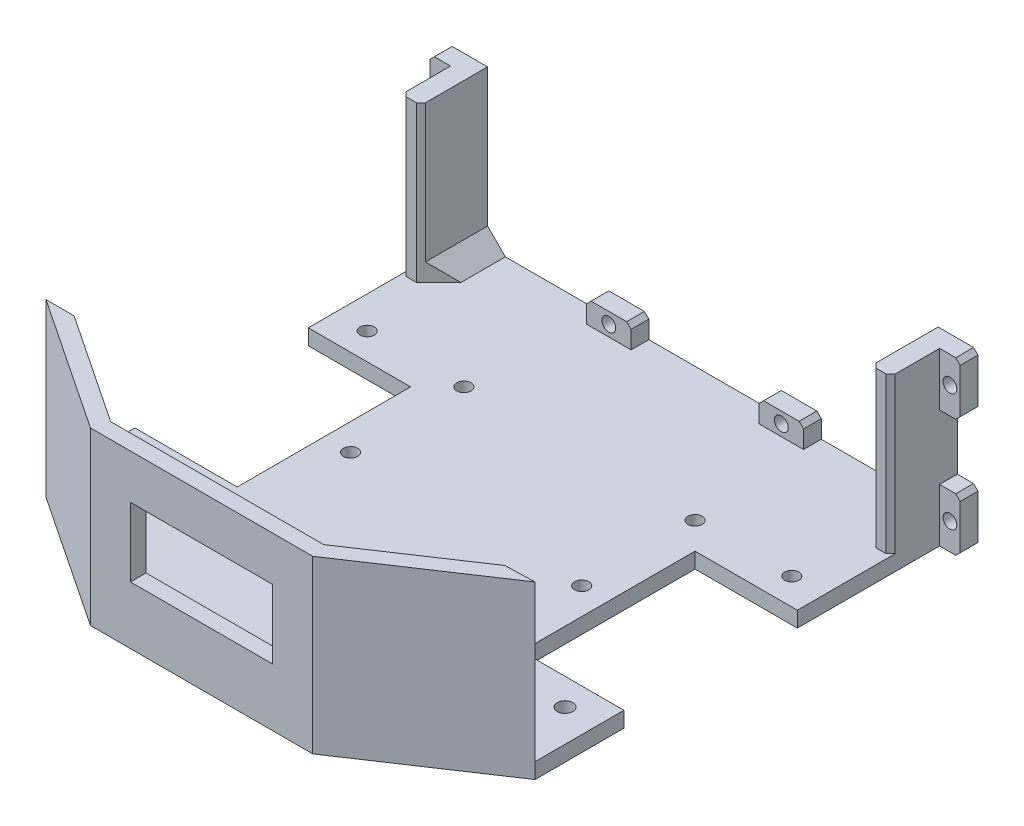
SolidWorks part; units mm, degrees
ref_plane "Front Plane" through (0, 0, 0) normal (0, 0, 1) x (1, 0, 0)
ref_plane "Top Plane" through (0, 0, 0) normal (0, 1, 0) x (1, 0, 0)
ref_plane "Right Plane" through (0, 0, 0) normal (1, 0, 0) x (0, 0, -1)
sketch "Sketch1" plane through (0, 0, 0) normal (0, 1, 0) x (1, 0, 0)
  line L0 (0, 40) -> (23, 40)
  line L1 (30, 0) -> (80, 0)
  line L2 (0, 20) -> (0, 40)
  line L3 (0, 100) -> (110, 100)
  line L4 (110, 20) -> (110, 40)
  line L5 (23, 40) -> (23, 79)
  line L6 (23, 79) -> (0, 79)
  line L7 (110, 79) -> (87, 79)
  line L8 (87, 79) -> (87, 40)
  line L9 (87, 40) -> (110, 40)
  line L10 (0, 79) -> (0, 100)
  line L11 (110, 79) -> (110, 100)
  line L12 (0, 20) -> (30, 0)
  line L13 (110, 20) -> (80, 0)
  point P0 (55, 0)
  dimension "D1" = 100
  dimension "D2" = 110
  dimension "23" = 23
  dimension "D4" = 40
  dimension "20" = 23
  dimension "D5" = 39
  dimension "40" = 40
extrude "Boss-Extrude1" add sketch "Sketch1" along normal blind 3.5 contours L1 L13 L4 L9 L8 L7 L11 L3 L10 L6 L5 L0 L2 L12
sketch "Sketch2" plane through (0, 3.5, 0) normal (0, 1, 0) x (1, 0, 0)
  line L0 (0, 79) -> (23, 79)
  line L1 (23, 79) -> (23, 40)
  line L2 (23, 40) -> (0, 40)
  line L3 (0, 40) -> (0, 37.5)
  line L4 (0, 40) -> (0, 20) construction
  line L5 (0, 37.5) -> (25.5, 37.5)
  line L6 (25.5, 37.5) -> (25.5, 81.5)
  line L7 (25.5, 81.5) -> (0, 81.5)
  line L8 (0, 100) -> (0, 79) construction
  line L9 (0, 81.5) -> (0, 79)
  line L10 (110, 81.5) -> (84.5, 81.5)
  line L11 (110, 79) -> (110, 100) construction
  line L12 (84.5, 81.5) -> (84.5, 37.5)
  line L13 (84.5, 37.5) -> (110, 37.5)
  line L14 (110, 20) -> (110, 40) construction
  line L15 (110, 37.5) -> (110, 40)
  line L16 (110, 40) -> (87, 40)
  line L17 (87, 40) -> (87, 79)
  line L18 (110, 81.5) -> (110, 79)
  line L19 (110, 79) -> (87, 79)
  dimension "D1" = 2.5
  dimension "3" = 2.5
  dimension "D2" = 2.5
  dimension "D3" = 2.5
  dimension "D4" = 2.5
  dimension "D5" = 2.5
extrude "Boss-Extrude2" add sketch "Sketch2" along normal blind 21
sketch "Sketch3" plane through (0, 24.5, 0) normal (0, 1, 0) x (1, 0, 0)
  line L1 (23, 79) -> (0, 79)
  line L2 (23, 79) -> (23, 40)
  line L3 (23, 40) -> (0, 40)
  line L4 (0, 79) -> (0, 40)
  line L5 (87, 79) -> (110, 79)
  line L6 (87, 79) -> (87, 40)
  line L7 (87, 40) -> (110, 40)
  line L8 (110, 79) -> (110, 40)
extrude "Boss-Extrude3" add sketch "Sketch3" against normal blind 2.5
sketch "Sketch5" plane through (0, 24.5, 0) normal (0, 1, 0) x (1, 0, 0)
  line L0 (55, 100) -> (55, 0) construction
  line L1 (110, 100) -> (0, 100) construction
  line L2 (30, 0) -> (80, 0) construction
  line L3 (110, 62.5) -> (131.5, 62.5)
  line L4 (0, 37.5) -> (-21.5, 37.5)
  line L5 (0, 37.5) -> (0, 62.5)
  line L6 (0, 62.5) -> (-21.5, 62.5)
  line L7 (-21.5, 37.5) -> (-21.5, 62.5)
  line L8 (131.5, 37.5) -> (131.5, 62.5)
  line L9 (110, 37.5) -> (131.5, 37.5)
  line L10 (110, 37.5) -> (110, 62.5)
  line L13 (25.5, 56.54) -> (25.5, 37.5)
  line L14 (25.5, 37.5) -> (32.57, 37.5)
  line L15 (32.57, 56.54) -> (32.57, 37.5)
  line L18 (84.5, 56.54) -> (84.5, 37.5)
  line L19 (84.5, 37.5) -> (77.43, 37.5)
  line L20 (77.43, 56.54) -> (77.43, 37.5)
  line L21 (25.5, 37.5) -> (25.5, 56.54) construction
  line L23 (25.5, 56.54) -> (32.57, 56.54)
  line L24 (77.43, 56.54) -> (84.5, 56.54) construction
  line L25 (84.5, 56.54) -> (77.43, 56.54)
  dimension "D1" = 21.5
  dimension "D2" = 25
extrude "Boss-Extrude5" add sketch "Sketch5" against normal blind 2.5
sketch "Sketch6" plane through (0, 24.5, 0) normal (0, 1, 0) x (1, 0, 0)
  line L0 (55, 100) -> (55, 0) construction
  line L1 (110, 100) -> (0, 100) construction
  line L2 (30, 0) -> (80, 0) construction
  line L3 (32.57, 37.5) -> (32.57, 56.54) construction
  line L4 (25.5, 56.54) -> (32.57, 56.54)
  line L5 (25.5, 56.54) -> (25.5, 50.64)
  line L6 (25.5, 50.64) -> (32.57, 50.64)
  line L7 (32.57, 56.54) -> (32.57, 50.64)
  line L8 (84.5, 50.64) -> (77.43, 50.64)
  line L9 (77.43, 56.54) -> (77.43, 50.64)
  line L10 (84.5, 56.54) -> (77.43, 56.54)
  line L11 (84.5, 56.54) -> (84.5, 50.64)
  line L12 (-21.5, 62.5) -> (-21.5, 37.5) construction
  line L13 (-21.5, 56.54) -> (-14.43, 56.54)
  line L14 (-21.5, 56.54) -> (-21.5, 50.64)
  line L15 (-21.5, 50.64) -> (-14.43, 50.64)
  line L16 (-14.43, 56.54) -> (-14.43, 50.64)
  line L17 (131.5, 50.64) -> (124.43, 50.64)
  line L18 (124.43, 56.54) -> (124.43, 50.64)
  line L19 (131.5, 56.54) -> (124.43, 56.54)
  line L20 (131.5, 56.54) -> (131.5, 50.64)
  dimension "D1" = 5.9
  dimension "D2" = 7.07
  dimension "D3" = 7.07
extrude "Boss-Extrude6" add sketch "Sketch6" along normal blind 20
sketch "Sketch7" plane through (0, 24.5, 0) normal (0, 1, 0) x (1, 0, 0)
  line L0 (55, 100) -> (55, 0) construction
  line L1 (110, 100) -> (0, 100) construction
  line L2 (30, 0) -> (80, 0) construction
  line L3 (25.5, 56.54) -> (25.5, 81.5) construction
  line L4 (0, 81.5) -> (25.5, 81.5)
  line L6 (0, 79) -> (25.5, 79)
  line L7 (25.5, 81.5) -> (25.5, 79)
  line L8 (110, 79) -> (84.5, 79)
  line L9 (84.5, 81.5) -> (84.5, 79)
  line L10 (110, 81.5) -> (84.5, 81.5)
  line L13 (0, 79) -> (-21.5, 79)
  line L15 (0, 81.5) -> (-21.5, 81.5)
  line L16 (-21.5, 79) -> (-21.5, 81.5)
  line L18 (110, 79) -> (131.5, 79)
  line L20 (110, 81.5) -> (131.5, 81.5)
  line L21 (131.5, 79) -> (131.5, 81.5)
  dimension "D1" = 2.5
extrude "Boss-Extrude7" add sketch "Sketch7" along normal blind 23
fillet "Fillet1" radius 10 4 edges at (0, 22, -38.75) (110, 22, -38.75) (110, 24.5, -80.25) (0, 24.5, -80.25)
sketch "Sketch9" plane through (0, 0, -81.5) normal (0, 0, -1) x (-1, 0, 0)
  line L0 (-131.5, 47.5) -> (-84.5, 47.5) construction
  line L3 (-131.5, 47.5) -> (-131.5, 24.5) construction
  line L4 (-55, 0) -> (-55, 48.0721) construction
  line L5 (-110, 0) -> (0, 0) construction
  circle A0 centre (-114.55, 34.35) radius 2.475
  circle A1 centre (4.55, 34.35) radius 2.475
  point P6 (-114.55, 34.35)
  dimension "D2" = 4.95
  dimension "D1" = 13.15
  dimension "D3" = 16.95
extrude "Boss-Extrude8" add sketch "Sketch9" along normal blind 9
fillet "Fillet2" radius 0.5 2 edges at (-2.075, 34.35, -90.5) (112.075, 34.35, -90.5)
sketch "Sketch10" plane through (0, 0, -50.64) normal (0, 0, 1) x (1, 0, 0)
  line L0 (55, 0) -> (55, 49.7444) construction
  line L1 (30, 0) -> (80, 0) construction
  line L2 (129.16, 44.5) -> (129.16, 24.5) construction
  line L3 (124.43, 44.5) -> (131.5, 44.5) construction
  line L4 (124.43, 24.5) -> (131.5, 24.5) construction
  line L5 (131.5, 44.5) -> (131.5, 24.5) construction
  line L6 (79.77, 44.5) -> (79.77, 24.5) construction
  line L7 (77.43, 44.5) -> (84.5, 44.5) construction
  line L8 (77.43, 24.5) -> (84.5, 24.5) construction
  line L9 (77.43, 44.5) -> (77.43, 24.5) construction
  circle A0 centre (129.16, 39.27) radius 1.65
  circle A1 centre (129.16, 29.43) radius 1.65
  circle A2 centre (79.77, 39.27) radius 1.65
  circle A3 centre (79.77, 29.43) radius 1.65
  circle A4 centre (-19.16, 29.43) radius 1.65
  circle A5 centre (-19.16, 39.27) radius 1.65
  circle A6 centre (30.23, 39.27) radius 1.65
  circle A7 centre (30.23, 29.43) radius 1.65
  dimension "D3" = 5.23
  dimension "D4" = 3.3
  dimension "D5" = 4.93
  dimension "D6" = 3.3
  dimension "D7" = 3.3
  dimension "D8" = 3.3
  dimension "D1" = 2.34
  dimension "D2" = 2.34
extrude "Cut-Extrude1" cut sketch "Sketch10" against normal blind 9
sketch "Sketch11" plane through (0, 0, -50.64) normal (0, 0, 1) x (1, 0, 0)
  line L0 (-21.5, 24.5) -> (-14.43, 24.5) construction
  line L1 (-14.43, 44.5) -> (-14.63, 44.5)
  line L2 (-14.43, 44.5) -> (-14.43, 24.5)
  line L3 (-14.43, 24.5) -> (-14.63, 24.5)
  line L4 (-14.63, 44.5) -> (-14.63, 24.5)
  line L5 (25.5, 24.5) -> (32.57, 24.5) construction
  line L6 (25.5, 44.5) -> (25.7, 44.5)
  line L7 (25.5, 44.5) -> (25.5, 24.5)
  line L8 (25.5, 24.5) -> (25.7, 24.5)
  line L9 (25.7, 44.5) -> (25.7, 24.5)
  line L10 (55, 3.5) -> (55, 47.4628) construction
  line L11 (30, 3.5) -> (80, 3.5) construction
  line L12 (84.5, 24.5) -> (84.3, 24.5)
  line L13 (84.3, 44.5) -> (84.3, 24.5)
  line L14 (84.5, 44.5) -> (84.3, 44.5)
  line L15 (84.5, 44.5) -> (84.5, 24.5)
  line L16 (124.43, 24.5) -> (124.63, 24.5)
  line L17 (124.63, 44.5) -> (124.63, 24.5)
  line L18 (124.43, 44.5) -> (124.63, 44.5)
  line L19 (124.43, 44.5) -> (124.43, 24.5)
  dimension "D1" = 0.2
  dimension "D2" = 0.2
extrude "Cut-Extrude2" cut sketch "Sketch11" against normal blind 9
sketch "Sketch12" plane through (0, 0, -81.5) normal (0, 0, -1) x (-1, 0, 0)
  line L0 (-108, 47.5) -> (-84.5, 25.5)
  line L1 (-131.5, 47.5) -> (-84.5, 47.5) construction
  line L2 (-84.5, 47.5) -> (-84.5, 3.5) construction
  line L3 (-84.5, 25.5) -> (-84.5, 47.5)
  line L4 (-84.5, 47.5) -> (-108, 47.5)
  line L5 (-55, 3.5) -> (-55, 47.5) construction
  line L6 (-110, 3.5) -> (0, 3.5) construction
  line L7 (-25.5, 25.5) -> (-25.5, 47.5)
  line L8 (-2, 47.5) -> (-25.5, 25.5)
  line L9 (-25.5, 47.5) -> (-2, 47.5)
  line L10 (-120, 24.5) -> (-131.5, 36)
  line L11 (-131.5, 47.5) -> (-131.5, 24.5) construction
  line L12 (-131.5, 36) -> (-131.5, 24.5)
  line L13 (-131.5, 24.5) -> (-120, 24.5)
  line L14 (10, 24.5) -> (21.5, 36)
  line L15 (21.5, 47.5) -> (21.5, 24.5) construction
  line L16 (21.5, 36) -> (21.5, 24.5)
  line L17 (21.5, 24.5) -> (10, 24.5)
extrude "Cut-Extrude3" cut sketch "Sketch12" against normal blind 9
fillet "Fillet3" radius 3 2 edges at (110, 23.25, -62.5) (0, 23.25, -62.5) profile chamfer
sketch "Sketch13" plane through (0, 3.5, 0) normal (0, 1, 0) x (1, 0, 0)
  line L0 (55, 100) -> (55, 0) construction
  line L1 (110, 100) -> (0, 100) construction
  line L2 (30, 0) -> (80, 0) construction
  line L3 (0, 30.5) -> (32.5, 30.5)
  line L4 (0, 37.5) -> (0, 20) construction
  line L5 (32.5, 30.5) -> (32.5, 88.5)
  line L6 (32.5, 88.5) -> (0, 88.5)
  line L7 (0, 100) -> (0, 81.5) construction
  line L8 (0, 88.5) -> (0, 81.5)
  line L9 (0, 81.5) -> (25.5, 81.5)
  line L10 (25.5, 81.5) -> (25.5, 37.5)
  line L11 (25.5, 37.5) -> (0, 37.5)
  line L12 (0, 37.5) -> (0, 30.5)
  line L13 (84.5, 37.5) -> (110, 37.5)
  line L14 (84.5, 81.5) -> (84.5, 37.5)
  line L15 (110, 81.5) -> (84.5, 81.5)
  line L16 (110, 88.5) -> (110, 81.5)
  line L17 (77.5, 88.5) -> (110, 88.5)
  line L18 (77.5, 30.5) -> (77.5, 88.5)
  line L19 (110, 30.5) -> (77.5, 30.5)
  line L20 (110, 37.5) -> (110, 30.5)
  dimension "D1" = 7
  dimension "D2" = 7
  dimension "D3" = 7
extrude "Boss-Extrude9" add sketch "Sketch13" along normal blind 5
sketch "Sketch14" plane through (0, 8.5, 0) normal (0, 1, 0) x (1, 0, 0)
  line L0 (55, 100) -> (55, 0) construction
  line L1 (110, 100) -> (0, 100) construction
  line L2 (30, 0) -> (80, 0) construction
  line L3 (0, 85) -> (29, 85) construction
  line L4 (0, 88.5) -> (0, 81.5) construction
  line L5 (29, 85) -> (29, 34) construction
  line L6 (29, 34) -> (0, 34) construction
  line L7 (0, 37.5) -> (0, 30.5) construction
  line L8 (32.5, 30.5) -> (32.5, 88.5) construction
  circle A0 centre (7.25, 34) radius 1.7478
  circle A3 centre (7.25, 85) radius 1.6
  circle A5 centre (29, 34) radius 1.6
  circle A6 centre (29, 59.5) radius 1.6
  circle A7 centre (29, 85) radius 1.6
  circle A8 centre (81, 34) radius 1.6
  circle A9 centre (102.75, 34) radius 1.7478
  circle A10 centre (81, 59.5) radius 1.6
  circle A11 centre (81, 85) radius 1.6
  circle A12 centre (102.75, 85) radius 1.6
  dimension "D2" = 3.2
  dimension "D3" = 7.25
  dimension "D4" = 3.2
  dimension "D6" = 3.2
  dimension "D7" = 7.25
  dimension "3.2" = 3.2
  dimension "D1" = 3.5
extrude "Cut-Extrude4" cut sketch "Sketch14" against normal blind 15
sketch "Sketch15" plane through (0, 3.5, 0) normal (0, 1, 0) x (1, 0, 0)
  line L0 (110, 20) -> (80, 0)
  line L1 (80, 0) -> (30, 0)
  line L2 (30, 0) -> (0, 20)
  line L3 (0, 20) -> (6.3097, 20)
  line L4 (6.3097, 20) -> (31.0597, 3.5)
  line L5 (31.0597, 3.5) -> (78.9403, 3.5)
  line L7 (78.9403, 3.5) -> (103.4055, 19.8101)
  line L9 (103.4055, 19.8101) -> (110, 20)
  dimension "D1" = 3.5
  dimension "D2" = 3.5
  dimension "D3" = 146.31
extrude "Boss-Extrude10" add sketch "Sketch15" along normal blind 35
sketch "Sketch17" plane through (0, 0, -100) normal (0, 0, -1) x (-1, 0, 0)
  line L1 (-110, 3.5) -> (0, 3.5)
  line L2 (-110, 3.5) -> (-110, 0)
  line L3 (-110, 0) -> (0, 0)
  line L4 (0, 3.5) -> (0, 0)
extrude "Boss-Extrude11" add sketch "Sketch17" along normal blind 15
sketch "Sketch18" plane through (0, 0, -88.5) normal (0, 0, -1) x (-1, 0, 0)
  line L1 (21.5, 47.5) -> (-139.9859, 47.5)
  line L2 (21.5, 47.5) -> (21.5, 3.5)
  line L3 (21.5, 3.5) -> (-139.9859, 3.5)
  line L4 (-139.9859, 47.5) -> (-139.9859, 3.5)
extrude "Cut-Extrude5" cut sketch "Sketch18" against normal blind 63
sketch "Sketch19" plane through (0, 3.5, 0) normal (0, 1, 0) x (1, 0, 0)
  line L0 (55, 115) -> (55, 9.3602) construction
  line L1 (0, 115) -> (110, 115) construction
  line L2 (110, 100) -> (105.6714, 100)
  line L3 (0, 115) -> (4.3286, 115)
  line L4 (0, 115) -> (0, 100)
  line L5 (0, 100) -> (4.3286, 100)
  line L6 (4.3286, 115) -> (4.3286, 100)
  line L7 (105.6714, 115) -> (105.6714, 100)
  line L8 (110, 115) -> (105.6714, 115)
  line L9 (110, 115) -> (110, 100)
  dimension "D1" = 15
extrude "Boss-Extrude12" add sketch "Sketch19" along normal blind 35
fillet "Fillet4" radius 1 4 edges at (110, 21, -100) (105.6714, 21, -100) (4.3286, 21, -100) (0, 21, -100) profile chamfer
sketch "Sketch20" plane through (0, 0, -115) normal (0, 0, -1) x (-1, 0, 0)
  line L0 (-55, 3.5) -> (-55, 38.5) construction
  line L1 (-110, 38.5) -> (-114.6401, 38.5)
  line L2 (-110, 38.5) -> (-110, 26.5)
  line L3 (-110, 26.5) -> (-114.6401, 26.5)
  line L4 (-114.6401, 38.5) -> (-114.6401, 26.5)
  line L5 (-110, 0) -> (-114.6401, 0)
  line L6 (-110, 0) -> (-110, 12)
  line L7 (-110, 12) -> (-114.6401, 12)
  line L8 (-114.6401, 0) -> (-114.6401, 12)
  line L9 (-78.9403, 3.5) -> (-31.0597, 3.5) construction
  line L10 (-78.9403, 38.5) -> (-31.0597, 38.5) construction
  line L11 (-112.32, 38.5) -> (-112.32, 26.5) construction
  line L12 (-112.32, 12) -> (-112.32, 0) construction
  line L13 (0, 12) -> (4.6401, 12)
  line L14 (4.6401, 0) -> (4.6401, 12)
  line L15 (0, 0) -> (4.6401, 0)
  line L16 (0, 0) -> (0, 12)
  line L17 (0, 26.5) -> (4.6401, 26.5)
  line L18 (4.6401, 38.5) -> (4.6401, 26.5)
  line L19 (0, 38.5) -> (4.6401, 38.5)
  line L20 (0, 38.5) -> (0, 26.5)
  line L21 (-79.4, 6) -> (-69.4, 6) construction
  line L22 (-79.4, 3.5) -> (-69.4, 3.5)
  line L23 (-79.4, 3.5) -> (-79.4, 8.5)
  line L24 (-79.4, 8.5) -> (-69.4, 8.5)
  line L25 (-69.4, 3.5) -> (-69.4, 8.5)
  line L26 (-30.6, 8.5) -> (-40.6, 8.5)
  line L27 (-40.6, 3.5) -> (-40.6, 8.5)
  line L28 (-30.6, 3.5) -> (-40.6, 3.5)
  line L29 (-30.6, 3.5) -> (-30.6, 8.5)
  circle A0 centre (-112.32, 32.5) radius 1.55
  circle A1 centre (-112.32, 6) radius 1.55
  circle A2 centre (2.32, 6) radius 1.55
  circle A3 centre (2.32, 32.5) radius 1.55
  circle A4 centre (-74.4, 6) radius 1.55
  circle A5 centre (-35.6, 6) radius 1.55
  dimension "D3" = 3.1
  dimension "D4" = 3.1
  dimension "D7" = 3.1
  dimension "D1" = 12
  dimension "D2" = 12
  dimension "D5" = 10
  dimension "D6" = 5
  dimension "D8" = 14.4
extrude "Boss-Extrude13" add sketch "Sketch20" against normal blind 4
sketch "Sketch21" plane through (0, 0, 0) normal (0, 0, 1) x (1, 0, 0)
  line L0 (30, 38.5) -> (80, 38.5) construction
  line L1 (39, 28.5) -> (71, 28.5)
  line L2 (39, 28.5) -> (39, 13)
  line L3 (39, 13) -> (71, 13)
  line L4 (71, 28.5) -> (71, 13)
  line L5 (30, 0) -> (80, 0) construction
  line L6 (30, 38.5) -> (30, 0) construction
  line L7 (80, 38.5) -> (80, 0) construction
  dimension "D1" = 10
  dimension "D2" = 13
  dimension "D3" = 9
  dimension "D4" = 9
extrude "Cut-Extrude6" cut sketch "Sketch21" against normal blind 14
fillet "Fillet5" radius 1 12 edges at (114.6401, 0, -113) (114.6401, 12, -113) (114.6401, 38.5, -113) (114.6401, 26.5, -113) (79.4, 8.5, -113) (69.4, 8.5, -113) (40.6, 8.5, -113) (30.6, 8.5, -113) (-4.6401, 0, -113) (-4.6401, 12, -113) (-4.6401, 26.5, -113) (-4.6401, 38.5, -113) profile chamfer
fillet "Fillet6" radius 4 2 edges at (4.3286, 3.5, -108) (105.6714, 3.5, -108) profile chamfer
